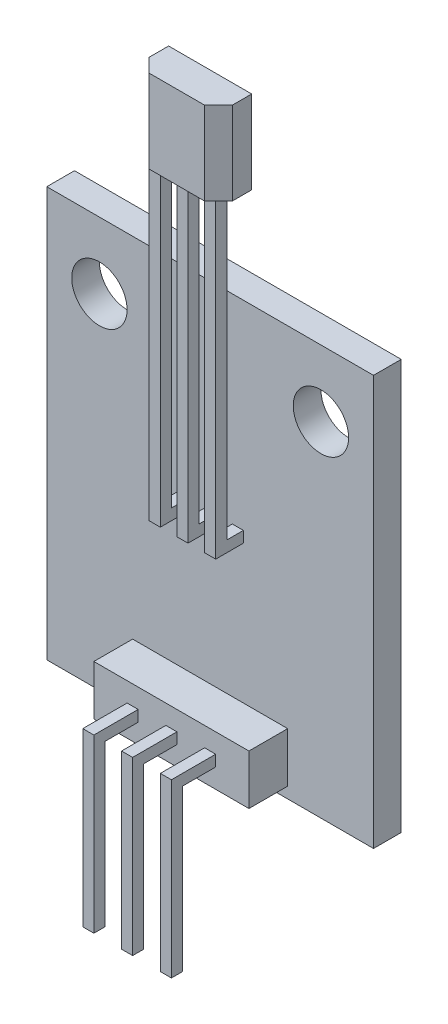
SolidWorks part; units mm, degrees
ref_plane "Front Plane" through (0, 0, 0) normal (0, 0, 1) x (1, 0, 0)
ref_plane "Top Plane" through (0, 0, 0) normal (0, 1, 0) x (1, 0, 0)
ref_plane "Right Plane" through (0, 0, 0) normal (1, 0, 0) x (0, 0, -1)
sketch "Sketch1" plane through (0, 0, 0) normal (0, 0, 1) x (1, 0, 0)
  line L1 (-7.493, 9.398) -> (7.493, 9.398)
  line L2 (-7.493, 9.398) -> (-7.493, -9.398)
  line L3 (-7.493, -9.398) -> (7.493, -9.398)
  line L4 (7.493, 9.398) -> (7.493, -9.398)
  line L5 (-7.493, 9.398) -> (7.493, -9.398) construction
  line L6 (-7.493, -9.398) -> (7.493, 9.398) construction
  point P0 (0, 0)
  dimension "D1" = 14.986
  dimension "D2" = 18.796
extrude "Boss-Extrude1" add sketch "Sketch1" along normal mid plane 1.27
sketch "Sketch2" plane through (0, 0, 0.635) normal (0, 0, 1) x (1, 0, 0)
  line L0 (-7.493, -9.398) -> (7.493, -9.398) construction
  line L1 (-3.556, -6.604) -> (3.556, -6.604)
  line L2 (-3.556, -6.604) -> (-3.556, -8.89)
  line L3 (-3.556, -8.89) -> (3.556, -8.89)
  line L4 (3.556, -6.604) -> (3.556, -8.89)
  line L5 (-3.556, -6.604) -> (3.556, -8.89) construction
  line L6 (-3.556, -8.89) -> (3.556, -6.604) construction
  point P0 (0, -7.747)
  dimension "D1" = 2.286
  dimension "D2" = 7.112
  dimension "D3" = 0.508
extrude "Boss-Extrude2" add sketch "Sketch2" along normal blind 1.778
sketch "Sketch3" plane through (0, 0, 2.413) normal (0, 0, 1) x (1, 0, 0)
  line L0 (-3.556, -6.604) -> (-3.556, -8.89) construction
  line L1 (-3.556, -7.747) -> (-1.778, -7.747) construction
  line L2 (-1.778, -7.747) -> (0, -7.747) construction
  line L3 (0, -7.747) -> (1.778, -7.747) construction
  line L4 (1.778, -7.747) -> (3.556, -7.747) construction
  line L5 (3.556, -8.89) -> (3.556, -6.604) construction
  line L7 (-2.032, -7.493) -> (-1.524, -7.493)
  line L8 (-2.032, -7.493) -> (-2.032, -8.001)
  line L9 (-2.032, -8.001) -> (-1.524, -8.001)
  line L10 (-1.524, -7.493) -> (-1.524, -8.001)
  line L11 (-2.032, -7.493) -> (-1.524, -8.001) construction
  line L12 (-2.032, -8.001) -> (-1.524, -7.493) construction
  line L13 (-0.254, -7.493) -> (0.254, -7.493)
  line L14 (-0.254, -7.493) -> (-0.254, -8.001)
  line L15 (-0.254, -8.001) -> (0.254, -8.001)
  line L16 (0.254, -7.493) -> (0.254, -8.001)
  line L17 (-0.254, -7.493) -> (0.254, -8.001) construction
  line L18 (-0.254, -8.001) -> (0.254, -7.493) construction
  line L19 (1.524, -7.493) -> (2.032, -7.493)
  line L20 (1.524, -7.493) -> (1.524, -8.001)
  line L21 (1.524, -8.001) -> (2.032, -8.001)
  line L22 (2.032, -7.493) -> (2.032, -8.001)
  line L23 (1.524, -7.493) -> (2.032, -8.001) construction
  line L24 (1.524, -8.001) -> (2.032, -7.493) construction
  dimension "D1" = 0.508
extrude "Boss-Extrude3" add sketch "Sketch3" along normal blind 2.032
sketch "Sketch4" plane through (0, -8.001, 0) normal (0, -1, 0) x (1, 0, 0)
  line L0 (-1.524, 4.445) -> (-1.524, 2.413) construction
  line L1 (-2.032, 4.445) -> (-1.524, 4.445)
  line L2 (-2.032, 4.445) -> (-2.032, 3.937)
  line L3 (-2.032, 3.937) -> (-1.524, 3.937)
  line L4 (-1.524, 4.445) -> (-1.524, 3.937)
  line L5 (-2.032, 4.445) -> (-1.524, 3.937) construction
  line L6 (-2.032, 3.937) -> (-1.524, 4.445) construction
  line L7 (-0.254, 4.445) -> (-0.254, 2.413) construction
  line L8 (-0.254, 3.937) -> (0.254, 3.937)
  line L9 (-0.254, 3.937) -> (-0.254, 4.445)
  line L10 (-0.254, 4.445) -> (0.254, 4.445)
  line L11 (0.254, 3.937) -> (0.254, 4.445)
  line L12 (-0.254, 3.937) -> (0.254, 4.445) construction
  line L13 (-0.254, 4.445) -> (0.254, 3.937) construction
  line L14 (2.032, 4.445) -> (2.032, 2.413) construction
  line L15 (1.524, 4.445) -> (2.032, 4.445)
  line L16 (1.524, 4.445) -> (1.524, 3.937)
  line L17 (1.524, 3.937) -> (2.032, 3.937)
  line L18 (2.032, 4.445) -> (2.032, 3.937)
  line L19 (1.524, 4.445) -> (2.032, 3.937) construction
  line L20 (1.524, 3.937) -> (2.032, 4.445) construction
  point P4 (-1.778, 4.191)
  point P12 (0, 4.191)
  point P20 (1.778, 4.191)
extrude "Boss-Extrude4" add sketch "Sketch4" along normal blind 7.366
sketch "Sketch5" plane through (0, 0, 0.635) normal (0, 0, 1) x (1, 0, 0)
  line L0 (0, 6.35) -> (-5.08, 6.35) construction
  line L1 (0, 6.35) -> (5.08, 6.35) construction
  line L2 (7.493, 9.398) -> (-7.493, 9.398) construction
  circle A0 centre (-5.08, 6.35) radius 1.27
  circle A1 centre (5.08, 6.35) radius 1.27
  dimension "D2" = 2.54
  dimension "D1" = 10.16
  dimension "D3" = 3.048
extrude "Cut-Extrude1" cut sketch "Sketch5" against normal through all both and the other way through all
sketch "Sketch6" plane through (0, 0, 0.635) normal (0, 0, 1) x (1, 0, 0)
  line L0 (2.032, -7.493) -> (1.524, -7.493) construction
  line L1 (-0.254, 0.254) -> (0.254, 0.254)
  line L2 (-0.254, 0.254) -> (-0.254, -0.254)
  line L3 (-0.254, -0.254) -> (0.254, -0.254)
  line L4 (0.254, 0.254) -> (0.254, -0.254)
  line L5 (-0.254, 0.254) -> (0.254, -0.254) construction
  line L6 (-0.254, -0.254) -> (0.254, 0.254) construction
  point P0 (0, 0)
extrude "Boss-Extrude5" add sketch "Sketch6" along normal blind 1.27
sketch "Sketch7" plane through (0, 0.254, 0) normal (0, 1, 0) x (1, 0, 0)
  line L0 (0.254, -1.905) -> (0.254, -0.635) construction
  line L1 (-0.254, -1.905) -> (0.254, -1.905)
  line L2 (-0.254, -1.905) -> (-0.254, -1.397)
  line L3 (-0.254, -1.397) -> (0.254, -1.397)
  line L4 (0.254, -1.905) -> (0.254, -1.397)
  line L5 (-0.254, -1.905) -> (0.254, -1.397) construction
  line L6 (-0.254, -1.397) -> (0.254, -1.905) construction
  point P4 (0, -1.651)
extrude "Boss-Extrude6" add sketch "Sketch7" along normal offset from surface (13.716 mm away) 4.572 up to face at (0, 9.398, 0) offset beyond the face yes
pattern_linear "LPattern1" count 2 spacing 1.27 along (1, 0, 0) of "Boss-Extrude5", "Boss-Extrude6"
mirror "Mirror1" about plane through (0, 0, 0) normal (1, 0, 0) of "LPattern1"
sketch "Sketch8" plane through (0, 13.97, 0) normal (0, 1, 0) x (1, 0, 0)
  line L0 (0, -2.794) -> (0, 2.794) construction
  line L1 (-1.905, -0.635) -> (1.905, -0.635)
  line L2 (-1.905, -0.635) -> (-1.905, -2.159)
  line L3 (-1.905, -2.159) -> (1.905, -2.159)
  line L4 (1.905, -0.635) -> (1.905, -2.159)
  line L5 (-1.905, -0.635) -> (1.905, -2.159) construction
  line L6 (-1.905, -2.159) -> (1.905, -0.635) construction
  line L7 (0.254, -1.905) -> (-0.254, -1.905) construction
  point P0 (0, -1.397)
  dimension "D1" = 0.254
  dimension "D2" = 1.524
  dimension "D3" = 3.81
extrude "Boss-Extrude7" add sketch "Sketch8" along normal blind 3.81
chamfer "Chamfer1" distance 0.635 angle 45 2 edges at (-1.905, 15.875, 2.159) (1.905, 15.875, 2.159)
